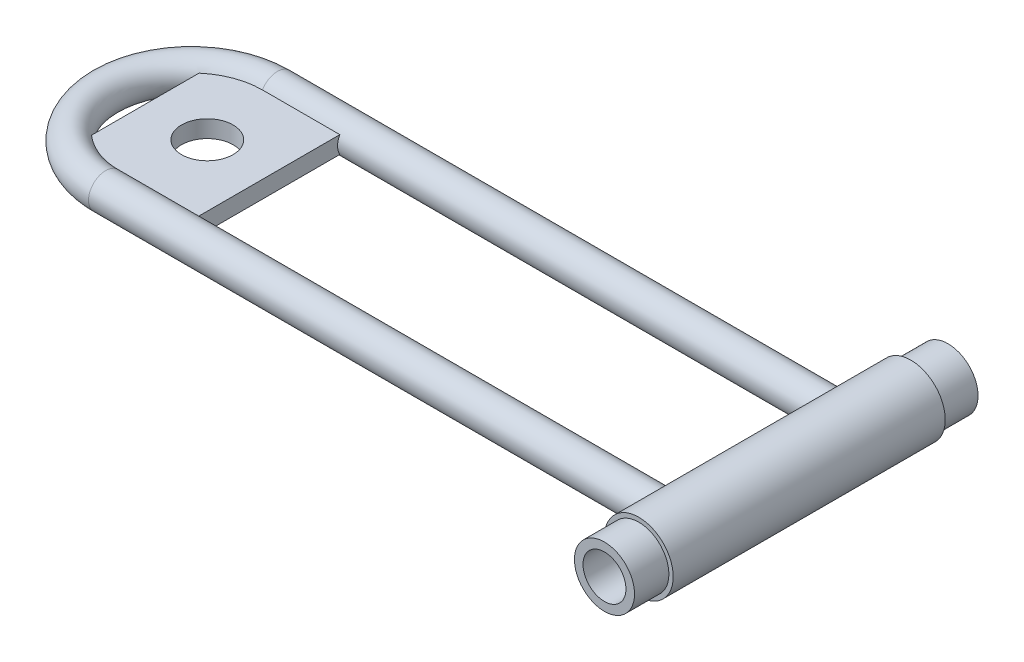
SolidWorks part; units mm, degrees
ref_plane "Front Plane" through (0, 0, 0) normal (0, 0, 1) x (1, 0, 0)
ref_plane "Top Plane" through (0, 0, 0) normal (0, 1, 0) x (1, 0, 0)
ref_plane "Right Plane" through (0, 0, 0) normal (1, 0, 0) x (0, 0, -1)
sketch "Sketch1" plane through (0, 0, 0) normal (0, 0, 1) x (1, 0, 0)
  circle A0 centre (0, 0) radius 6.35
  circle A1 centre (0, 0) radius 3.175
  dimension "D1" = 12.7
  dimension "D2" = 3.175
extrude "Boss-Extrude1" add sketch "Sketch1" along normal blind 62.992
ref_plane "Plane1" through (-3.81, 0, 0) normal (-1, 0, 0) x (0, 0, 1)
sketch "Sketch3" plane through (-3.81, 0, 0) normal (-1, 0, 0) x (0, 0, 1)
  line L0 (0, 0) -> (62.992, 0)
  line L1 (62.992, -6.35) -> (62.992, 6.35) construction
  circle A0 centre (-15.748, 0) radius 3.175
  circle A1 centre (47.244, 0) radius 3.175
  dimension "D3" = 6.35
  dimension "D4" = 6.35
  dimension "D1" = 15.748
  dimension "D2" = 15.748
sketch "Sketch4" plane through (0, 0, 0) normal (0, 1, 0) x (1, 0, 0)
  line L0 (-3.81, -15.6639) -> (-107.95, -15.6639)
  line L1 (-3.81, 0) -> (-3.81, -62.992) construction
  line L2 (-3.81, -47.0944) -> (-107.95, -47.0944)
  line L3 (-6.35, 0) -> (-6.35, -62.992) construction
  arc A0 (-107.95, -15.6639) -> (-107.95, -47.0944) centre (-107.95, -31.3792) ccw
  dimension "D1" = 101.6
sweep "Sweep1" add profiles "Sketch3" path "Sketch4"
ref_plane "Plane2" through (0, 0, 15.24) normal (0, 0, 1) x (1, 0, 0)
sketch "Sketch6" plane through (0, 0, 15.24) normal (0, 0, 1) x (1, 0, 0)
  line L0 (-116.5013, 0) -> (-93.6413, 0)
  line L3 (-93.6413, 0) -> (-116.5013, 0)
  line L4 (-93.6413, 0) -> (-93.6413, -1.5875)
  line L5 (-93.6413, -1.5875) -> (-116.5013, -1.5875)
  line L6 (-116.5013, 0) -> (-116.5013, -1.5875)
  line L7 (-93.6413, 0) -> (-116.5013, 0)
  line L8 (-93.6413, 0) -> (-93.6413, 1.5875)
  line L9 (-93.6413, 1.5875) -> (-116.5013, 1.5875)
  line L10 (-116.5013, 0) -> (-116.5013, 1.5875)
  point P3 (-105.0713, 0)
  dimension "D1" = 22.86
  dimension "D2" = 1.5875
  dimension "D3" = 1.5875
extrude "Boss-Extrude3" add sketch "Sketch6" along normal blind 29.21 contours L0 L6 L5 L4 | L10 L0 L8 L9 region at (-105.0713, 0.7937, 15.24) region at (-105.0713, -0.7937, 15.24)
sketch "Sketch7" plane through (0, 1.5875, 0) normal (0, 1, 0) x (1, 0, 0)
  line L1 (-93.6413, -44.45) -> (-93.6413, -18.2639) construction
  circle A0 centre (-105.0713, -31.3411) radius 4.7625
  dimension "D3" = 9.525
  dimension "D1" = 11.43
  dimension "D2" = 9.906
extrude "Cut-Extrude1" cut sketch "Sketch7" against normal blind 29.21
sketch "Sketch9" plane through (0, 0, 0) normal (0, 0, -1) x (-1, 0, 0)
  circle A0 centre (0, 0) radius 6.35
  circle A1 centre (0, 0) radius 3.175
ref_plane "Plane3" through (0, 0, 31.496) normal (0, 0, 1) x (1, 0, 0)
extrude "Boss-Extrude5" add sketch "Sketch9" along normal blind 6.35
mirror "Mirror1" about plane through (0, 0, 31.496) normal (0, 0, 1) of "Boss-Extrude5"
sketch "Sketch10" plane through (0, 0, 69.342) normal (0, 0, 1) x (1, 0, 0)
  circle A0 centre (0, 0) radius 5.5562
  circle A1 centre (0, 0) radius 6.35
  dimension "D1" = 11.1125
  dimension "D2" = 12.7
extrude "Cut-Extrude6" cut sketch "Sketch10" against normal blind 12.7
sketch "Sketch12" plane through (0, 0, -6.35) normal (0, 0, -1) x (-1, 0, 0)
  circle A0 centre (0, 0) radius 5.5562
  circle A1 centre (0, 0) radius 6.35
  dimension "D1" = 11.1125
extrude "Cut-Extrude7" cut sketch "Sketch12" against normal blind 12.7
sketch "Sketch13" plane through (0, 0, 69.342) normal (0, 0, 1) x (1, 0, 0)
  circle A0 centre (0, 0) radius 5.5563
  circle A1 centre (0, 0) radius 3.175
  circle A2 centre (0, 0) radius 3.175 construction
  dimension "D1" = 6.35
  dimension "D2" = 11.1125
extrude "Cut-Extrude8" cut sketch "Sketch13" against normal blind 6.35
sketch "Sketch14" plane through (0, 0, -6.35) normal (0, 0, -1) x (-1, 0, 0)
  circle A0 centre (0, 0) radius 5.5563
  circle A1 centre (0, 0) radius 3.175
  circle A2 centre (0, 0) radius 3.175 construction
  dimension "D1" = 6.35
  dimension "D2" = 11.1125
extrude "Cut-Extrude9" cut sketch "Sketch14" against normal blind 6.35
sketch "Sketch16" plane through (0, 0, 0) normal (0, 0, -1) x (-1, 0, 0)
  circle A0 centre (0, 0) radius 3.9688
  dimension "D1" = 7.9375
extrude "Cut-Extrude11" cut sketch "Sketch16" against normal through all
sketch "Sketch18" plane through (0, 0, 0) normal (0, 0, -1) x (-1, 0, 0)
  circle A0 centre (0, 0) radius 5.5563
  circle A1 centre (0, 0) radius 3.9688
  circle A2 centre (0, 0) radius 3.9688 construction
  dimension "D1" = 7.9375
  dimension "D2" = 11.1125
extrude "Boss-Extrude7" add sketch "Sketch18" along normal blind 0.508
